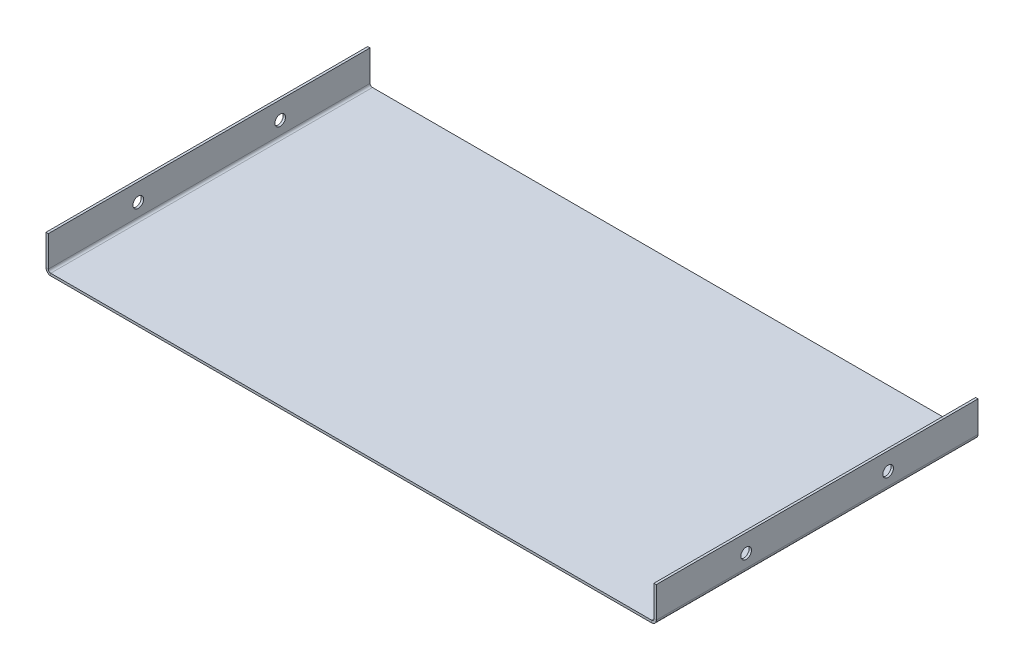
SolidWorks part; units mm, degrees
note: The reader was unsure of these and kept them because the rebuilt part matched: flange length of "Edge-Flange1", "Edge-Flange2".
material "AISI 1020"
ref_plane "Front Plane" through (0, 0, 0) normal (0, 0, 1) x (1, 0, 0)
ref_plane "Top Plane" through (0, 0, 0) normal (0, 1, 0) x (1, 0, 0)
ref_plane "Right Plane" through (0, 0, 0) normal (1, 0, 0) x (0, 0, -1)
sketch "Sketch1" plane through (0, 0, 0) normal (0, 1, 0) x (1, 0, 0)
  line L1 (0, 0) -> (256, 0)
  line L2 (0, 0) -> (0, 136)
  line L3 (0, 136) -> (256, 136)
  line L4 (256, 0) -> (256, 136)
  dimension "D1" = 256
  dimension "D2" = 136
base flange "Base-Flange1" sketch "Sketch1" thickness 1 reverse thickness direction no parameters "D1"=1
edge flange "Edge-Flange1" sketch "Sketch8" flange angle 90 flange length 15 flange position material outside bend radius 1 thickness 1 relief rectangular parameters "D6"=10
sketch "Sketch8" plane through (0, 0, 0) normal (-1, 0, 0) x (0, 0, 1)
  line L0 (-136, 0) -> (0, 0) construction
  line L1 (-136, 0) -> (0, 0)
  line L2 (-136, 0) -> (-136, 14)
  line L3 (-136, 14) -> (0, 14)
  line L4 (0, 14) -> (0, 0)
bend "EdgeBend1" bend radius 1 bend angle 90 parameters "D5"=1
edge flange "Edge-Flange2" sketch "Sketch11" flange angle 90 flange length 15 flange position material outside bend radius 1 thickness 1 relief rectangular parameters "D6"=10
sketch "Sketch11" plane through (256, 0, 0) normal (1, 0, 0) x (0, 0, -1)
  line L0 (0, 0) -> (136, 0) construction
  line L1 (0, 0) -> (136, 0)
  line L2 (0, 0) -> (0, 14)
  line L3 (0, 14) -> (136, 14)
  line L4 (136, 14) -> (136, 0)
bend "EdgeBend2" bend radius 1 bend angle 90 parameters "D5"=2
extrude "Cut-Extrude1" cut sketch "Sketch12" against normal blind 278
sketch "Sketch12" plane through (-2, -333.4, -193.0625) normal (-1, 0, 0) x (0, 1, 0)
  line L0 (339.9, -73.287) -> (339.9, -197.4958) construction
  circle A0 centre (339.9, -95.0625) radius 2.25
  circle A1 centre (339.9, -155.0625) radius 2.25
sketch "Bend-Lines1" [suppressed] plane through (0, 0, 0) normal (0, 1, 0) x (1, 0, 0)
sketch "Bounding-Box1" [suppressed] plane through (0, 0, 0) normal (0, 1, 0) x (1, 0, 0)
sheet metal parameters "Sheet-Metal1" thickness 1 parameters "D1"=1
flat pattern "Flat-Pattern1" [suppressed]
sketch "Bend-Lines2" plane through (0, 0, 0) normal (0, 1, 0) x (1, 0, 0)
sketch3d "Bounding-Box2" [suppressed]
  line L0 (-260, 140, 0) -> (0, 140, 0) construction
  line L1 (-260, 0, 0) -> (0, 0, 0) construction
  line L2 (-260, 140, 0) -> (-260, 0, 0) construction
  line L3 (0, 140, 0) -> (0, 0, 0) construction
sheet metal parameters "Sheet-Metal2" thickness 1 parameters "D1"=1
flat pattern "Flat-Pattern1"
sketch "Bend-Lines2" plane through (0, 0, 0) normal (0, 1, 0) x (1, 0, 0)
  line L0 (-0.1781, 140) -> (-0.1781, 0) construction
  line L1 (-0.1781, 140) -> (-0.1781, 0) construction
sketch3d "Bounding-Box2" [suppressed]
  line L0 (260, 140, 0) -> (-14.3562, 140, 0) construction
  line L1 (260, 0, 0) -> (-14.3562, 0, 0) construction
  line L2 (260, 140, 0) -> (260, 0, 0) construction
  line L3 (-14.3562, 140, 0) -> (-14.3562, 0, 0) construction
bend of the flat pattern "Flatten-<EdgeBend1>1"
sheet metal parameters "Sheet-Metal3" thickness 1 parameters "D1"=1
flat pattern "Flat-Pattern1"
sketch "Bend-Lines2" plane through (0, 0, 0) normal (0, 1, 0) x (1, 0, 0)
  line L0 (-0.1781, 136) -> (-0.1781, 0) construction
  line L1 (-0.1781, 136) -> (-0.1781, 0) construction
  line L2 (256.1781, 0) -> (256.1781, 136) construction
  line L3 (256.1781, 0) -> (256.1781, 136) construction
sketch3d "Bounding-Box2" [suppressed]
  line L0 (270.3562, 136, 0) -> (-14.3562, 136, 0) construction
  line L1 (270.3562, 0, 0) -> (-14.3562, 0, 0) construction
  line L2 (270.3562, 136, 0) -> (270.3562, 0, 0) construction
  line L3 (-14.3562, 136, 0) -> (-14.3562, 0, 0) construction
bend of the flat pattern "Flatten-<EdgeBend1>1"
bend of the flat pattern "Flatten-<EdgeBend2>1"
sheet metal parameters "Sheet-Metal4" thickness 1 parameters "D1"=1
flat pattern "Flat-Pattern1"
sketch "Bend-Lines2" plane through (0, 0, 0) normal (0, 1, 0) x (1, 0, 0)
  line L0 (-0.1781, 136) -> (-0.1781, 0) construction
  line L1 (-0.1781, 136) -> (-0.1781, 0) construction
  line L2 (256.1781, 0) -> (256.1781, 136) construction
  line L3 (256.1781, 0) -> (256.1781, 136) construction
sketch3d "Bounding-Box2" [suppressed]
  line L0 (270.3562, 136, 0) -> (-14.3562, 136, 0) construction
  line L1 (270.3562, 0, 0) -> (-14.3562, 0, 0) construction
  line L2 (270.3562, 136, 0) -> (270.3562, 0, 0) construction
  line L3 (-14.3562, 136, 0) -> (-14.3562, 0, 0) construction
bend of the flat pattern "Flatten-<EdgeBend1>1"
bend of the flat pattern "Flatten-<EdgeBend2>1"
